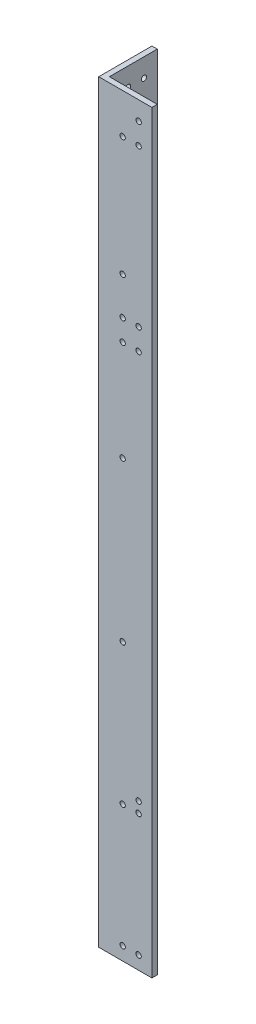
SolidWorks part; units mm, degrees
ref_plane "Front Plane" through (0, 0, 0) normal (0, 0, 1) x (1, 0, 0)
ref_plane "Top Plane" through (0, 0, 0) normal (0, 1, 0) x (1, 0, 0)
ref_plane "Right Plane" through (0, 0, 0) normal (1, 0, 0) x (0, 0, -1)
sketch "Sketch2" plane through (0, 0, 0) normal (0, 1, 0) x (1, 0, 0)
  line L0 (0, 31.75) -> (3.175, 31.75)
  line L1 (3.175, 31.75) -> (3.175, 3.175)
  line L2 (3.175, 3.175) -> (31.75, 3.175)
  line L3 (31.75, 3.175) -> (31.75, 0)
  line L4 (31.75, 0) -> (0, 0)
  line L5 (0, 0) -> (0, 31.75)
  point P9 (1.5875, 31.75)
  point P10 (31.75, 1.5875)
  dimension "D4" = 3.175
  dimension "D1" = 31.75
  dimension "D2" = 31.75
  dimension "D3" = 3.175
extrude "Boss-Extrude1" add sketch "Sketch2" along normal blind 450
sketch "RightSideHoles-Sketch3" plane through (0, 0, 0) normal (0, 0, 1) x (1, 0, 0)
  line L0 (0, 0) -> (31.75, 0) construction
  line L1 (0, 450) -> (31.75, 450) construction
  line L3 (0, 450) -> (0, 0) construction
  circle A0 centre (14.2875, 81.1125) radius 1.5875
  circle A1 centre (23.8125, 81.1125) radius 1.5875
  circle A3 centre (23.8125, 87.4625) radius 1.5875
  circle A5 centre (14.2875, 426.1875) radius 1.5875
  circle A6 centre (23.8125, 438.8875) radius 1.5875
  circle A7 centre (23.8125, 426.1875) radius 1.5875
  circle A8 centre (14.2875, 332.6026) radius 1.5875
  circle A9 centre (23.8125, 332.6026) radius 1.5875
  circle A10 centre (14.2875, 319.9026) radius 1.5875
  circle A11 centre (23.8125, 319.9026) radius 1.5875
  circle A12 centre (14.2875, 7.9375) radius 1.5875
  circle A13 centre (23.8125, 7.9375) radius 1.5875
  circle A14 centre (14.2875, 165) radius 1.5875
  circle A15 centre (14.2875, 260) radius 1.5875
  circle A16 centre (14.2875, 355) radius 1.5875
  dimension "D4" = 3.175
  dimension "D1" = 81.1125
  dimension "D2" = 14.2875
  dimension "D12" = 7.9375
  dimension "D7" = 12.7
  dimension "D3" = 9.525
  dimension "D10" = 332.6026
  dimension "D11" = 165
  dimension "D13" = 95
  dimension "D14" = 95
  dimension "D5" = 6.35
  dimension "D6" = 12.7
  dimension "D8" = 11.1125
sketch "FrontSideHoles-Sketch4" plane through (0, 0, 0) normal (-1, 0, 0) x (0, 0, 1)
  line L0 (-31.75, 450) -> (0, 450) construction
  line L1 (0, 450) -> (0, 0) construction
  line L3 (-31.75, 0) -> (0, 0) construction
  circle A0 centre (-23.8125, 81.1125) radius 1.5875
  circle A2 centre (-23.8125, 87.4625) radius 1.5875
  circle A3 centre (-14.2875, 87.4625) radius 1.5875
  circle A4 centre (-23.8125, 438.8875) radius 1.5875
  circle A5 centre (-14.2875, 438.8875) radius 1.5875
  circle A6 centre (-23.8125, 426.1875) radius 1.5875
  circle A8 centre (-14.2875, 338.1776) radius 2
  circle A9 centre (-14.2875, 319.6526) radius 2
  circle A10 centre (-14.2875, 165) radius 1.5875
  circle A11 centre (-14.2875, 260) radius 1.5875
  circle A12 centre (-14.2875, 355) radius 1.5875
  circle A13 centre (-23.8125, 7.9375) radius 1.5875
  circle A14 centre (-14.2875, 7.9375) radius 1.5875
  dimension "D4" = 3.175
  dimension "D7" = 12.7
  dimension "D13" = 95
  dimension "D14" = 95
  dimension "D5" = 6.35
  dimension "D16" = 4
  dimension "D6" = 11.1125
  dimension "D9" = 18.525
  dimension "D10" = 14.2875
  dimension "D8" = 319.6526
  dimension "D12" = 165
  dimension "D15" = 7.9375
  dimension "D2" = 14.2875
  dimension "D11" = 9.525
  dimension "D3" = 81.1125
extrude "RightSideHoles-Cut-Extrude1" cut sketch "RightSideHoles-Sketch3" against normal blind 3.175
extrude "FrontSideHoles-Cut-Extrude2" cut sketch "FrontSideHoles-Sketch4" against normal blind 3.175
equation "\"RailThickness\"= .125in'Spec"
equation "\"VSWidth\"= 1.25in'Spec"
equation "\"VSHeight\"= 1.25in'Spec"
equation "\"VSLength\"= 450mm"
equation "\"HoleOffsetFromEdge\"= \"RailThickness\" * 2.5"
equation "\"HoleOffsetFromSide\"= \"RailThickness\" * 3.5"
equation "\"LegHeight\"= 70mm'Space needed for PSU/Stepper/Electronics"
equation "\"VSBottomSideRailHoleY1FromBottomOfLowerRail\"= \"V1 BottomOfLowerRail\" + \"HoleOffsetFromSide\"'Equals 70.1125"
equation "\"VSSideRailHoleX1FromSide\"= \"HoleOffsetFromSide\" + \"RailThickness\""
equation "\"FasteningHoleDiameter\"= .125in"
equation "\"VSBottomSideRailHoleY2FromY1\"= \"LowerRailHeight\" - \"HoleOffsetFromSide\" - \"HoleOffsetFromEdge\"'Equals 6.35"
equation "\"VSTopSideRailHoleY1FromEdge\"= \"HoleOffsetFromEdge\" + \"RailThickness\""
equation "\"D4@RightSideHoles-Sketch3\" = \"FasteningHoleDiameter\""
equation "\"D1@RightSideHoles-Sketch3\" = \"VSBottomSideRailHoleY1FromBottomOfLowerRail\""
equation "\"D2@RightSideHoles-Sketch3\" = \"VSSideRailHoleX1FromSide\""
equation "\"D1@Boss-Extrude1\"=\"VSLength\""
equation "\"D4@FrontSideHoles-Sketch4\" = \"FasteningHoleDiameter\""
equation "\"D6@FrontSideHoles-Sketch4\" = \"VSTopSideRailHoleY1FromEdge\""
equation "\"VSMidSideRailHoleY1FromV8TopOfMidSideRail\"= \"V8 ToTopOfMidSideRail\" - \"HoleOffsetFromEdge\"'Equals 308.2875"
equation "\"LowerRailHeight\"= 1.00in"
equation "\"D2@Sketch2\"=\"VSWidth\""
equation "\"D1@Sketch2\"=\"VSHeight\""
equation "\"TopRailHeight\"= 1.25in"
equation "\"MidSideRailHeight\"= 1.25in"
equation "\"D12@RightSideHoles-Sketch3\"=\"HoleOffsetFromEdge\""
equation "\"VSMidSideRailHoleY2FromY1\"= \"MidSideRailHeight\" - \"HoleOffsetFromSide\" - \"HoleOffsetFromEdge\"'Equals 12.7"
equation "\"D7@RightSideHoles-Sketch3\"=\"VSMidSideRailHoleY2FromY1\""
equation "\"VSTopSideRailHoleY2FromY1\"= \"TopRailHeight\" - \"VSTopSideRailHoleY1FromEdge\" - \"HoleOffsetFromEdge\"'Equals 12.7"
equation "\"D7@FrontSideHoles-Sketch4\"=\"VSTopSideRailHoleY2FromY1\""
equation "\"VSSideRailHoleX2FromX1\"= \"VSWidth\" - \"VSSideRailHoleX1FromSide\" - \"HoleOffsetFromEdge\""
equation "\"D3@RightSideHoles-Sketch3\"=\"VSSideRailHoleX2FromX1\""
equation "\"1mmSpacer\"= 1mm"
equation "\"20TGT2PulleyWidth\"= 8.7mm'The STL of the Pulley in the diagram is a bit larger"
equation "\"BeltTensionerUpperLowerWallThickness\"= 7mm"
equation "\"BeltTensionerInnerHeight\"= \"20TGT2PulleyWidth\" * 2 + \"1mmSpacer\" * 3"
equation "\"BeltTensionerHeight\"= \"BeltTensionerInnerHeight\" + \"BeltTensionerUpperLowerWallThickness\" * 2"
equation "\"D9@FrontSideHoles-Sketch4\"=\"VSBeltTensionerHoleY2FromY1\""
equation "\"VSBeltTensionerHoleY1FromBottom\"= \"V9 FromBottomGantryPulleyToBottomOfBeltTensioner\" + \"HoleOffsetFromEdge\""
equation "\"VSBeltTensionerHoleY2FromY1\"= \"BeltTensionerHeight\" - \"HoleOffsetFromEdge\" * 2"
equation "\"V1 BottomOfLowerRail\"= \"LegHeight\""
equation "\"StepperShaftLength\"= 24mm'Pulley will be attached to the end"
equation "\"ZAxisLeadScrewLength\"= 200mm"
equation "\"LM8UUHeight\"= 24mm'Spec"
equation "\"V2 ToBedAtTopOfZAxis\"= \"V1 BottomOfLowerRail\" + \"StepperShaftLength\" + \"ZAxisLeadScrewLength\" - \"LM8UUHeight\" / 2"
equation "\"HotEndToTopOfXAxisGB\"= 63.315144mm'Measured from the100.Should be 63.315144"
equation "\"TopOfGBToBottomOfLinearRail\"= \"LinearGBWidth\" / 2 + \"LinearRailWidth\" / 2"
equation "\"LinearGBWidth\"= 27mm'Spec"
equation "\"V5 ToBottomOfXAxisLinearRail\"= \"V4 ToTopOfBuildPlate/HotEndTip\" + \"HotEndToTopOfXAxisGB\" - \"TopOfGBToBottomOfLinearRail\""
equation "\"LinearRailWidth\"= 12mm'Spec"
equation "\"V6 ToBottomOfGantryPulley\"= \"V5 ToBottomOfXAxisLinearRail\" - \"DistanceFromGABTopToLowerPulley\""
equation "\"GABUpperHeight\"= 6mm"
equation "\"GABMidWallHeight\"= 28mm'Must equal 28 or changes alignment"
equation "\"GABMidShortRiserHeight\"= \"GABMidWallHeight\" / 2 - \"20TGT2PulleyWidth\"'Equals 5.3"
equation "\"GABRiserBossOffset\"= 0.8mm'Aligns Pulleys"
equation "\"DistanceFromGABTopToLowerPulley\"= \"GABUpperHeight\" + \"GABMidWallHeight\" - \"GABMidShortRiserHeight\" + \"GABRiserBossOffset\" / 2"
equation "\"V7 ToTopOfMidBackRail\"= \"V6 ToBottomOfGantryPulley\" + \"StepperShaftLength\""
equation "\"D10@RightSideHoles-Sketch3\"=\"VSMidSideRailHoleY1FromV8TopOfMidSideRail\""
equation "\"BedToBuildPlateStandoffLength\"= 15mm"
equation "\"BuildPlateHeight\"= 8mm'Spec"
equation "\"V4 ToTopOfBuildPlate/HotEndTip\"= \"V2 ToBedAtTopOfZAxis\" + \"BedToBuildPlateStandoffLength\" + \"BuildPlateHeight\""
equation "\"D8@FrontSideHoles-Sketch4\"=\"VSBeltTensionerHoleY1FromBottom\""
equation "\"V8 ToTopOfMidSideRail\"= \"V7 ToTopOfMidBackRail\" - \"RailThickness\""
equation "\"V9 FromBottomGantryPulleyToBottomOfBeltTensioner\"= \"V6 ToBottomOfGantryPulley\" - \"BeltTensionerUpperLowerWallThickness\" - \"1mmSpacer\""
equation "\"BeltTensionerMountingHoleOffsetFromEdge\"= \"HoleOffsetFromEdge\""
equation "\"VSBeltTensionerXMountingHoleOffsetFromSide\"= \"BeltTensionerMountingHoleOffsetFromEdge\" + \"RailThickness\" * 2"
equation "\"D10@FrontSideHoles-Sketch4\"=\"VSBeltTensionerXMountingHoleOffsetFromSide\""
equation "\"VSEnclosureOffsets\"= ( \"VSLength\" - \"LegHeight\" ) / 4"
equation "\"D11@RightSideHoles-Sketch3\"=\"LegHeight\" + \"VSEnclosureOffsets\""
equation "\"D13@RightSideHoles-Sketch3\"=\"VSEnclosureOffsets\""
equation "\"D14@RightSideHoles-Sketch3\"=\"VSEnclosureOffsets\""
equation "\"D12@FrontSideHoles-Sketch4\"= \"LegHeight\" + \"VSEnclosureOffsets\""
equation "\"D13@FrontSideHoles-Sketch4\"=\"VSEnclosureOffsets\""
equation "\"D14@FrontSideHoles-Sketch4\"=\"VSEnclosureOffsets\""
equation "\"D15@FrontSideHoles-Sketch4\"=\"HoleOffsetFromEdge\""
equation "\"D2@FrontSideHoles-Sketch4\"=\"VSSideRailHoleX1FromSide\""
equation "\"D5@FrontSideHoles-Sketch4\"=\"VSBottomSideRailHoleY2FromY1\""
equation "\"D3@FrontSideHoles-Sketch4\"=\"VSBottomSideRailHoleY1FromBottomOfLowerRail\""
equation "\"D5@RightSideHoles-Sketch3\"=\"VSBottomSideRailHoleY2FromY1\""
equation "\"D6@RightSideHoles-Sketch3\"=\"VSTopSideRailHoleY2FromY1\""
equation "\"D8@RightSideHoles-Sketch3\"=\"VSTopSideRailHoleY1FromEdge\""
equation "\"BeltTensionerMountingHoleDiameter\" = 4.0mm"
equation "\"D16@FrontSideHoles-Sketch4\"=\"BeltTensionerMountingHoleDiameter\""
